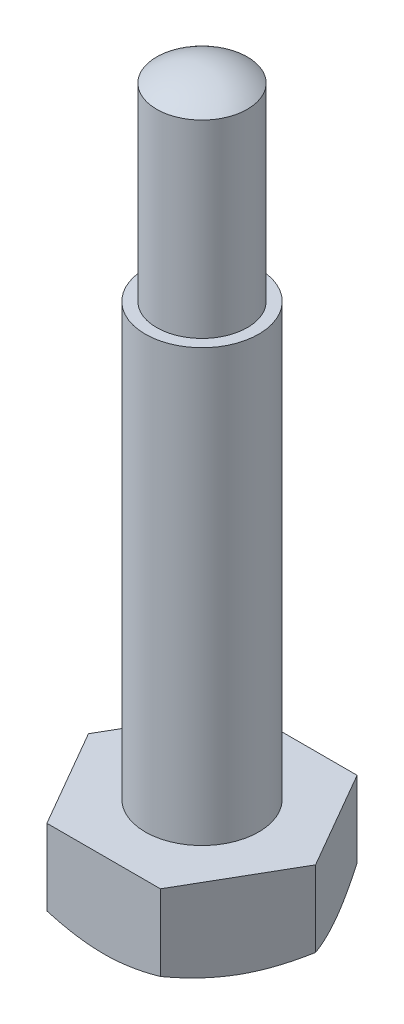
SolidWorks part; units mm, degrees
note: The reader was unsure of these and kept them because the rebuilt part matched: shared geometry of "Sketch1<3>", "Sketch1<4>".
ref_plane "Front Plane" through (0, 0, 0) normal (0, 0, 1) x (1, 0, 0)
ref_plane "Top Plane" through (0, 0, 0) normal (0, 1, 0) x (1, 0, 0)
ref_plane "Right Plane" through (0, 0, 0) normal (1, 0, 0) x (0, 0, -1)
sketch "Sketch1" plane through (0, 0, 0) normal (0, 1, 0) x (1, 0, 0)
  line L1 (15.0111, 0) -> (7.5056, 13)
  line L2 (7.5056, 13) -> (-7.5056, 13)
  line L3 (-7.5056, 13) -> (-15.0111, 0)
  line L4 (-15.0111, 0) -> (-7.5056, -13)
  line L5 (-7.5056, -13) -> (7.5056, -13)
  line L6 (7.5056, -13) -> (15.0111, 0)
  circle A0 centre (0, 0) radius 13 construction
  circle A1 centre (0, 0) radius 7.5
  circle A2 centre (0, 0) radius 6
extrude "Boss-Extrude1" add sketch "Sketch1" along normal blind 11.2 contours L5 L6 L1 L2 L3 L4 A1 | A2 | A1 A2
extrude "Boss-Extrude2" add sketch "Sketch1<3>" along normal blind 68.2 contours A1 A2
sketch "Sketch1<3>" plane through (0, 0, 0) normal (0, 1, 0) x (1, 0, 0) same geometry as "Sketch1"
extrude "Boss-Extrude3" add sketch "Sketch1<4>" along normal blind 93.2 contours A2
sketch "Sketch1<4>" plane through (0, 0, 0) normal (0, 1, 0) x (1, 0, 0) same geometry as "Sketch1"
cosmetic thread "Cosmetic Thread1" parameters "D2"=10.072
sketch "Sketch2" plane through (0, 0, 0) normal (0, 0, 1) x (1, 0, 0)
  line L1 (6, 93.2) -> (-6, 93.2) construction
  line L2 (-6, 93.2) -> (0, 93.2)
  line L3 (0, 93.2) -> (0, 95.2)
  arc A1 (0, 95.2) -> (-6, 93.2) centre (0, 85.2) ccw
sketch "Sketch4" plane through (0, 0, 0) normal (0, -1, 0) x (1, 0, 0)
  circle A0 centre (0, 0) radius 13
extrude "Cut-Extrude1" cut sketch "Sketch4" against normal blind 82.5 draft 60 flip side to cut
revolve "Revolve2" add sketch "Sketch2" angle 360 about L3
